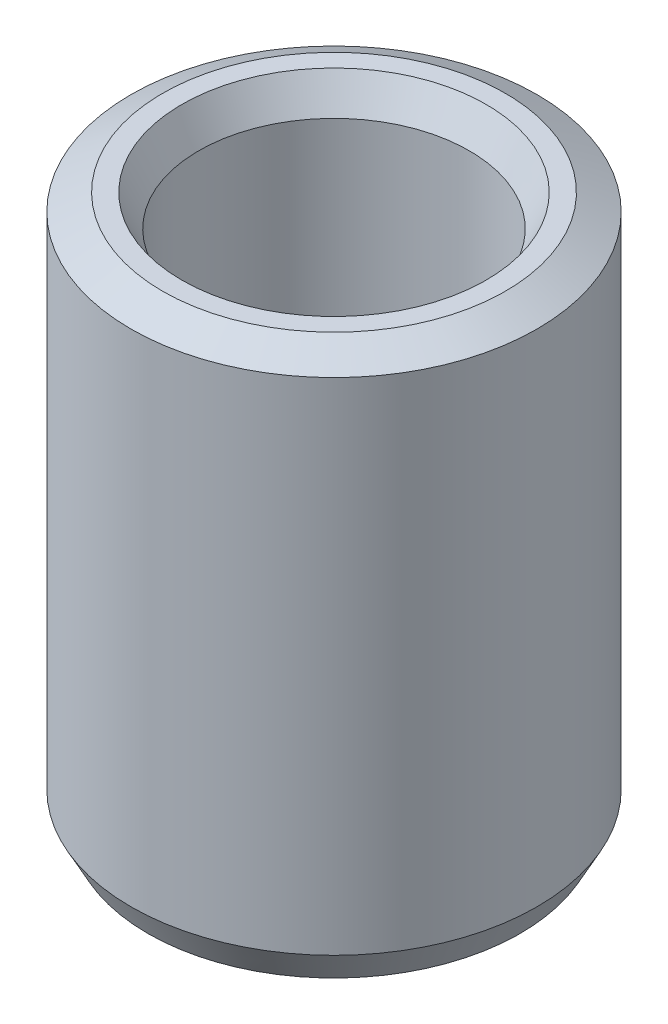
SolidWorks part; units mm, degrees
ref_plane "Front Plane" through (0, 0, 0) normal (0, 0, 1) x (1, 0, 0)
ref_plane "Top Plane" through (0, 0, 0) normal (0, 1, 0) x (1, 0, 0)
ref_plane "Right Plane" through (0, 0, 0) normal (1, 0, 0) x (0, 0, -1)
sketch "Sketch1" plane through (0, 0, 0) normal (0, 1, 0) x (1, 0, 0)
  circle A0 centre (0, 0) radius 47.5
  dimension "SLEEVE_OD" = 95
extrude "Boss-Extrude1" add sketch "Sketch1" along normal blind 128.3974
sketch "Sketch2" plane through (0, 0, 0) normal (0, 1, 0) x (1, 0, 0)
  circle A0 centre (0, 0) radius 31.6443
  dimension "BORE_D" = 63.2885
extrude "Cut-Extrude1" cut sketch "Sketch2" along normal through all
chamfer "Chamfer1" distance 3.9575 angle 61.859 4 edges at (0, 128.3974, 31.6443) (0, 0, 31.6443) (0, 0, 47.5) (0, 128.3974, 47.5) first distance on face at (0, 128.3974, 31.6443) first distance on face at (0, 0, 31.6443) first distance on face at (0, 128.3974, 47.5)
